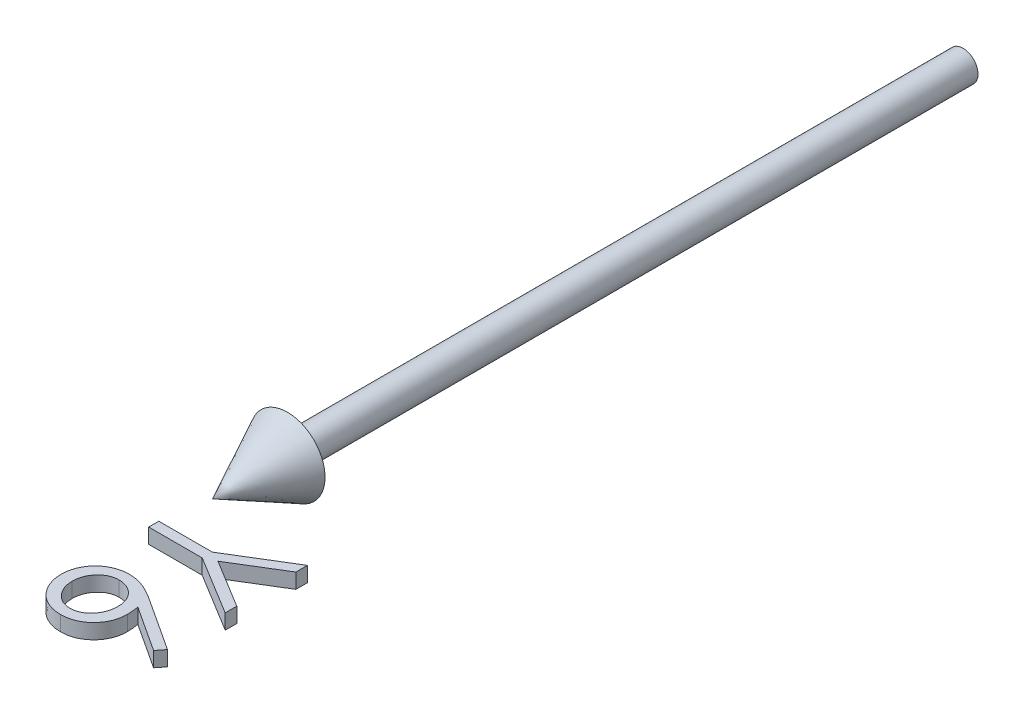
SolidWorks part; units mm, degrees
ref_plane "Front Plane" through (0, 0, 0) normal (0, 0, 1) x (1, 0, 0)
ref_plane "Top Plane" through (0, 0, 0) normal (0, 1, 0) x (1, 0, 0)
ref_plane "Right Plane" through (0, 0, 0) normal (1, 0, 0) x (0, 0, -1)
sketch "Sketch2" plane through (0, 0, 0) normal (0, 1, 0) x (1, 0, 0)
  line L0 (0, 41.95) -> (0, -114.4521) construction
  line L1 (-36.8894, 0) -> (41.4965, 0) construction
  line L2 (0, -100) -> (5, -90)
  line L3 (5, -90) -> (2, -90)
  line L4 (2, -90) -> (2, 0)
  line L5 (2, 0) -> (0, 0)
  line L6 (0, 0) -> (0, -100)
  dimension "D1" = 100
  dimension "D2" = 2
  dimension "D3" = 10
  dimension "D4" = 5
revolve "Revolve1" add sketch "Sketch2" angle 360 about L0
sketch "Sketch3" plane through (0, 0, 0) normal (0, 1, 0) x (1, 0, 0)
  line L0 (0, -101.5706) -> (0, -127.8138) construction
  text T0 "Y6\r\n\r\n\r\n" font "Century Gothic" height 15
extrude "Boss-Extrude1" add sketch "Sketch3" against normal blind 1 and the other way blind 1 separate body
equation "\"frame_arrow_length\"=100"
equation "\"D1@Sketch2\"=\"frame_arrow_length\""
equation "\"frame_arrow_odA\"=4"
equation "\"D2@Sketch2\"=\"frame_arrow_odA\"/2"
equation "\"frame_arrow_head_od\"=5"
equation "\"D4@Sketch2\"=\"frame_arrow_head_od\""
equation "\"frame_arrow_head_length\"=10"
equation "\"D3@Sketch2\"=\"frame_arrow_head_length\""
equation "\"tvarobot_theta1\"=30"
equation "\"link0_ringA_odA\"= 40"
equation "\"link0_ringA_odB\"= 25"
equation "\"link0_ringA_id\"= 20"
equation "\"link0_ringA_thickness\"= (\"link0_ringA_odB\" - \"link0_ringA_id\")/2"
equation "\"link0_ringA_height\"= 3"
equation "\"link0_ringA_heightA\"= 1.5"
equation "\"link0_ringA_heightB\"=\"link0_ringA_height\"-\"link0_ringA_heightA\""
equation "\"link0_ringB_odA\"= 40"
equation "\"link0_ringB_odB\"= 29"
equation "\"link0_ringB_id\"= \"link0_shaftA_bearing_id\"+1"
equation "\"link0_ringB_thickness\"= (\"link0_ringB_odB\" - \"link0_ringB_id\")/2"
equation "\"link0_ringB_height\"= 3"
equation "\"link0_ringB_heightA\"= 1.5"
equation "\"link0_ringB_heightB\"=\"link0_ringB_height\"-\"link0_ringB_heightA\""
equation "\"link0_shaftA_bearing_od\"=27"
equation "\"link0_shaftA_bearing_id\"=20"
equation "\"link0_shaftA_thrust_bearing_od\"=35"
equation "\"link0_shaftA_thrust_bearing_id\"=20.04"
equation "\"link0_shaftA_retaining_ring_id\"=18.5"
equation "\"link0_shaftA_retaining_ring_groove_width\"=1.5"
equation "\"link0_shaftA_spline_length\"=8.0"
equation "\"link0_shaftA_spline_depth\"=1.0"
equation "\"link0_shaftA_spline_width\"=4.0"
equation "\"link0_shaftA_odA\"=\"link0_shaftA_bearing_id\""
equation "\"link0_shaftA_odB\"=35"
equation "\"link0_shaftA_odC\"=\"link0_shaftA_bearing_id\""
equation "\"link0_shaftA_odD\"=\"link0_shaftA_odC\"-2*\"link0_shaftA_spline_depth\""
equation "\"link0_shaftA_odE\"=\"link0_shaftA_bearing_id\""
equation "\"link0_shaftA_odF\"=\"link0_shaftA_odE\"-2*\"link0_shaftA_spline_depth\""
equation "\"link0_shaftA_idA\"=10"
equation "\"link0_shaftA_idB\"=6"
equation "\"link0_shaftA_length\"=39.5"
equation "\"link0_shaftA_lengthA\"=8.0"
equation "\"link0_shaftA_lengthB\"=12.0"
equation "\"link0_shaftA_lengthC\"=35.0"
equation "\"link0_shaftA_lengthD\"=39.0"
equation "\"link0_shaftA_lengthE\"=\"link0_shaftA_length\"-\"link0_shaftA_lengthD\""
equation "\"link0_shaftA_offsetX\"=11"
equation "\"link0_shaftA_offsetY\"=0"
equation "\"link0_shaftA_bolt_pattern_dia\"=14"
equation "\"link0_motor_center_dist\"=26"
equation "\"link0_46t_pulley_spline_length\"=8"
equation "\"link0_46t_pulley_spline_depth\"=\"link0_shaftA_spline_depth\"*1.025"
equation "\"link0_46t_pulley_spline_width\"=\"link0_shaftA_spline_width\"*1.05"
equation "\"link0_46t_pulley_idA\"=\"link0_shaftA_bearing_id\"*1.025"
equation "\"link0_46t_pulley_idB\"=\"link0_46t_pulley_idA\"-2*\"link0_46t_pulley_spline_depth\""
equation "\"link0_shaftB_spline_length\"=10"
equation "\"link0_shaftB_spline_depth\"=1.0"
equation "\"link0_shaftB_spline_width\"=1.25"
equation "\"link0_shaftB_length\"=7"
equation "\"link0_shaftB_lengthA\"=1.5"
equation "\"link0_shaftB_lengthB\"=2.75"
equation "\"link0_shaftB_odA\"=32"
equation "\"link0_shaftB_odB\"=22"
equation "\"link0_shaftB_odC\"=20"
equation "\"link0_shaftB_idA\"=10"
equation "\"link0_shaftB_bolt_diameter\"=19"
equation "\"link0_shaftB_bearing_od\"=27"
equation "\"link0_shaftB_bearing_id\"=20"
equation "\"link0_motor_length\"=46.5"
equation "\"link0_motor_width\"=28.5"
equation "\"link0_motor_height\"=34"
equation "\"link0_motor_offset\"=8"
equation "\"link0_shellA_thickness\"=2.5"
equation "\"link0_shellB_thickness\"=\"link0_shellA_thickness\""
equation "\"link0_plateA_shellA_height\"=48"
equation "\"link0_shellA_width\" =\"link0_plateA_width\""
equation "\"link0_shellA_height\" = \"link0_plateA_shellA_height\"-\"link0_plateA_height\""
equation "\"link0_shellA_length\" = \"link0_plateA_lengthB\" "
equation "\"link0_shellB_length\"=\"link0_shellA_length\""
equation "\"link0_shellA_radius\" = 0.375*25.4"
equation "\"link0_shellA_radiusA\"= \"link0_plateA_radiusA\""
equation "\"link0_shellA_radiusB\"= \"link0_plateA_radiusB\""
equation "\"link0_shellA_radiusC\"= 3"
equation "\"link0_postA_height\"=7"
equation "\"link0_postA_width\"=16"
equation "\"link0_postA_length\"=20"
equation "\"link0_postA_posX\"=22"
equation "\"link0_postA_posY\"=17.5"
equation "\"link0_postA_pocket_width\"=6.0"
equation "\"link0_postA_pocket_length\"=2.5"
equation "\"link0_postA_pocket_depth\"=9"
equation "\"link0_postA_pocket_posZ\"=10"
equation "\"link0_postB_height\"=7"
equation "\"link0_postB_width\"=16"
equation "\"link0_postB_length\"=20"
equation "\"link0_postB_posX\"=22"
equation "\"link0_postB_posY\"=17.5"
equation "\"link0_postB_id\"=3.0"
equation "\"link0_postB_pocket_width\"=6.0"
equation "\"link0_postB_pocket_length\"=2.5"
equation "\"link0_postB_pocket_depth\"=9"
equation "\"link0_postB_pocket_posZ\"=10"
equation "\"link0_postC_height\"=7"
equation "\"link0_postC_width\"=16"
equation "\"link0_postC_length\"=20"
equation "\"link0_postC_posX\"=22"
equation "\"link0_postC_posY\"=17.5"
equation "\"link0_postC_id\"=3.0"
equation "\"link0_postC_pocket_width\"=6.0"
equation "\"link0_postC_pocket_length\"=2.5"
equation "\"link0_postC_pocket_depth\"=9"
equation "\"link0_postC_pocket_posZ\"=10"
equation "\"link0_postD_height\"=7"
equation "\"link0_postD_width\"=16"
equation "\"link0_postD_length\"=20"
equation "\"link0_postD_posX\"=22"
equation "\"link0_postD_posY\"=17.5"
equation "\"link0_postD_id\"=3.0"
equation "\"link0_postD_pocket_width\"=6.0"
equation "\"link0_postD_pocket_length\"=3.0"
equation "\"link0_postD_pocket_depth\"=9"
equation "\"link0_postD_pocket_posZ\"=10"
equation "\"link0_postE_height\"=5"
equation "\"link0_postE_width\"=16"
equation "\"link0_postE_length\"=\"link0_plateE_lengthA\"-\"link0_lip_height\""
equation "\"link0_postE_posZ\"=22"
equation "\"link0_postE_posX\"=17.5"
equation "\"link0_postE_posY\"=22"
equation "\"link0_postE_id\"=3.0"
equation "\"link0_postE_cbore_id\"=6.5"
equation "\"link0_postE_hole_id\"=3"
equation "\"link0_postF_posZ\"=22"
equation "\"link0_postF_posX\"=17.5"
equation "\"link0_postF_posY\"=\"link0_plateB_lengthA\"+4"
equation "\"link0_postF_id\"=3.0"
equation "\"link0_postF_cbore_id\"=6.5"
equation "\"link0_postF_hole_id\"=3"
equation "\"link0_postG_posZ\"=22"
equation "\"link0_postG_posX\"=17.5"
equation "\"link0_postG_posY\"=\"link0_plateB_lengthA\"+12"
equation "\"link0_postG_id\"=3.0"
equation "\"link0_postG_cbore_id\"=6.5"
equation "\"link0_postG_hole_id\"=3"
equation "\"link0_postHIJ_posY\"=6"
equation "\"link0_postH_posX\"=28"
equation "\"link0_postH_posY\"=20"
equation "\"link0_postH_posZ\"=20"
equation "\"link0_postH_length\"=10"
equation "\"link0_postI_posX\"=28"
equation "\"link0_postI_posY\"=20"
equation "\"link0_postI_posZ\"=135"
equation "\"link0_postI_length\"=10"
equation "\"link0_postJ_posX\"=28"
equation "\"link0_postJ_posY\"=20"
equation "\"link0_postJ_posZ\"=175"
equation "\"link0_postJ_length\"=10"
equation "\"link0_postK_posX\"=28"
equation "\"link0_postK_posY\"=20"
equation "\"link0_postK_posZ\"=175"
equation "\"link0_postK_length\"=10"
equation "\"link0_postL_posX\"=28"
equation "\"link0_postL_posY\"=20"
equation "\"link0_postL_posZ\"=135"
equation "\"link0_postL_length\"=10"
equation "\"link0_postM_posX\"=28"
equation "\"link0_postM_posY\"=20"
equation "\"link0_postM_posZ\"=35"
equation "\"link0_postM_length\"=10"
equation "\"link0_plateA_lengthA\"=30"
equation "\"link0_plateA_lengthB\"=150"
equation "\"link0_plateA_lengthC\"=30"
equation "\"link0_plateA_length\"=\"link0_plateA_lengthA\"+\"link0_plateA_lengthB\"+\"link0_plateA_lengthC\""
equation "\"link0_plateA_width\"=  68"
equation "\"link0_plateA_height\"= \"link0_plateA_radiusA\""
equation "\"link0_plateA_thickness\"=\"link0_shellA_thickness\""
equation "\"link0_plateA_radius\"= 9.5"
equation "\"link0_plateA_radiusA\"= 18"
equation "\"link0_plateA_radiusB\"= 18"
equation "\"link0_plateA_radiusC\"= 3"
equation "\"link0_plateB_length\"= 40"
equation "\"link0_plateB_width\"= \"link0_plateA_width\"*1.005"
equation "\"link0_plateB_height\"= \"link0_plateA_shellA_height\"*1.005"
equation "\"link0_plateB_lengthA\"=\"link0_lip_height\"+\"link0_plateD_thickness\"+\"link0_motor_mount_thickness\""
equation "\"link0_plateB_lengthB\"=\"link0_plateB_height\"-\"link0_plateB_lengthA\""
equation "\"link0_plateB_radiusA\"= \"link0_plateA_radiusA\""
equation "\"link0_plateB_radiusB\"= \"link0_plateA_radiusB\""
equation "\"link0_plateB_radiusC\"= 3"
equation "\"link0_plateB_idA\"=\"link0_shaftA_odC\"+1"
equation "\"link0_plateB_idB\"=\"link0_shaftA_bearing_od\"-2"
equation "\"link0_plateB_idC\"=\"link0_shaftA_bearing_od\"*1.005"
equation "\"link0_plateB_idD\"=\"link0_shaftA_thrust_bearing_od\"+1 "
equation "\"link0_plateB_depthA\"=1.0"
equation "\"link0_plateB_depthB\"=2.0"
equation "\"link0_plateB_depthC\"=8"
equation "\"link0_plateB_depthD\"=\"link0_plateB_length\"-\"link0_lip_height\"-\"link0_plateD_thickness\" "
equation "\"link0_plateC_length\"=\"link0_plateB_length\""
equation "\"link0_plateC_width\"= \"link0_plateB_width\""
equation "\"link0_plateC_height\"= .1*25.4"
equation "\"link0_plateA_hole_od\" = 0.1*25.4"
equation "\"link0_plateA_hole_delx\" = 0.5*25.4"
equation "\"link0_plateA_hole_delz\" = 0.75*25.4"
equation "\"link0_plateA_hole_offx\" = 0.0*25.4"
equation "\"link0_plateA_hole_offz\" = \"link0_plateA_length\"/2"
equation "\"link0_plateB_hole_od\" = 0.1*25.4"
equation "\"link0_plateB_hole_delx\"= 0.75*25.4"
equation "\"link0_plateB_hole_delz\"= 0.75*25.4"
equation "\"link0_plateB_hole_offx\"= 0.0*25.4"
equation "\"link0_plateB_hole_offz\"= 0.0*25.4"
equation "\"link0_plateC_hole_od\"= 0.1*25.4"
equation "\"link0_plateC_hole_delx\"= 0.75*25.4"
equation "\"link0_plateC_hole_delz\"= 0.75*25.4"
equation "\"link0_plateC_hole_offx\"= 0.0*25.4"
equation "\"link0_plateC_hole_offz\"= 0.0*25.4"
equation "\"link0_plateD_height\"=\"link0_plateB_height\"-2*\"link0_shellA_thickness\""
equation "\"link0_plateD_width\"=\"link0_plateB_width\"-2*\"link0_shellA_thickness\""
equation "\"link0_plateD_thickness\"=10"
equation "\"link0_plateD_radiusA\"=\"link0_plateB_radiusA\"-\"link0_shellA_thickness\""
equation "\"link0_plateD_odA\"= .375*25.4"
equation "\"link0_plateD_odB\"= .375*25.4"
equation "\"link0_plateD_bearing_id\"=20"
equation "\"link0_plateD_bearing_od\"=27"
equation "\"link0_plateE_radiusA\"=\"link0_plateA_radiusA\""
equation "\"link0_plateE_radiusB\"=\"link0_plateA_radiusB\""
equation "\"link0_plateE_radiusC\"=8.0"
equation "\"link0_plateE_length\"=30"
equation "\"link0_plateE_lengthA\"=16"
equation "\"link0_plateE_height\"=\"link0_plateB_height\""
equation "\"link0_plateE_width\"=\"link0_plateB_width\""
equation "\"link0_plateE_odA\"=\"gantry_coupler_id\"*0.99"
equation "\"link0_plateE_idA\"=\"link0_plateE_odA\"-20.0"
equation "\"link0_plateE_spline_depth\"=\"link0_poleA_spline_depth\"*1.05"
equation "\"link0_plateE_spline_width\"=\"link0_poleA_spline_width\"*1.075"
equation "\"link0_plateE_spline_length\"=\"link0_poleA_spline_length\""
equation "\"link0_plateE_coupler_length\"=46"
equation "\"link0_lip_height\"=5.0"
equation "\"link0_lip_thickness\"=2.0"
equation "\"link0_motor_mount_thickness\"=8.0"
equation "\"link0_motor_mount_idA\"=22"
equation "\"link0_motor_mount_idB\"=\"link0_shaftB_bearing_od\"*1.005"
equation "\"link0_motor_mount_idC\"=\"link0_shaftB_bearing_od\"-2"
equation "\"link0_motor_mount_depthA\"=5.5"
equation "\"link0_motor_mount_height\"=\"link0_plateD_height\""
equation "\"link0_motor_mount_width\"=\"link0_plateD_width\""
equation "\"link0_motor_mountL_height\"=36"
equation "\"link0_motor_mountL_heightA\"=12"
equation "\"link0_motor_mountL_length\"=50"
equation "\"link0_motor_mountL_lengthA\"=36"
equation "\"gantry_coupler_od\"=25.4*2.0"
equation "\"gantry_coupler_id\"=1.645*25.4"
equation "\"gantry_coupler_offsetX\"=\"link0_plateE_width\"/2"
equation "\"link0_poleA_odA\"=20"
equation "\"link0_poleA_odB\"=36"
equation "\"link0_poleA_idA\"=\"link0_poleA_odA\"-2*\"link0_poleA_thickness\""
equation "\"link0_poleA_idB\"=(\"link0_plateE_idA\"/2+1.5*\"link0_lip_thickness\")*1.04"
equation "\"link0_poleA_thickness\"=3.5"
equation "\"link0_poleA_length\"=100"
equation "\"link0_poleA_lengthA\"=18.5"
equation "\"link0_poleA_lengthB\"=80"
equation "\"link0_poleA_gasket_thickness\"=1.5"
equation "\"link0_poleA_spline_depth\"=1.0"
equation "\"link0_poleA_spline_width\"=4.0"
equation "\"link0_poleA_spline_length\"=10.0"
equation "\"link1_plateB_length\"=30"
equation "\"link1_lip_height\"=\"link0_lip_height\""
equation "\"link0_tension_plateA_width\"=12"
equation "\"link0_tension_plateA_lengthA\"=10.5"
equation "\"link0_tension_plateB_width\"=\"link0_tension_plateA_width\""
equation "\"link0_tension_plateB_lengthA\"=\"link0_tension_plateA_lengthA\""
equation "\"link0_tension_wheelA_posZ\"=7"
equation "\"link0_tension_wheelA_posX\"=\"link0_plateD_height\"/2-\"link0_tension_plateA_lengthA\""
equation "\"link0_m2_clear_hole_id\"=2.35"
equation "\"link0_m2_insert_hole_id\"=2.5"
equation "\"link0_m2_tap_hole_id\"=1.75"
equation "\"link0_m2_nut_socket_width\"=4.25"
equation "\"link0_m2_nut_socket_depth\"=2.5"
equation "\"link0_m2_cbore_id\"=3.75"
equation "\"link0_m2_cbore_depth\"=7"
equation "\"link0_m2_5_clear_hole_id\"=2.75"
equation "\"link0_m2_5_insert_hole_id\"=2.75"
equation "\"link0_m2_5_tap_hole_id\"=2.25"
equation "\"link0_m2_5_nut_socket_width\"=5.25"
equation "\"link0_m2_5_nut_socket_depth\"=2.5"
equation "\"link0_m2_5_cbore_id\"=4.75"
equation "\"link0_m2_5_cbore_depth\"=2.5"
equation "\"link0_m2_5_insert_access_length\"=6.0"
equation "\"link0_m2_5_insert_access_width\"=3.0"
equation "\"link0_m3_clear_hole_id\"=3.25"
equation "\"link0_m3_insert_hole_id\"=3"
equation "\"link0_m3_tap_hole_id\"=2.75"
equation "\"link0_m3_nut_socket_width\"=5.75"
equation "\"link0_m3_nut_socket_depth\"=4.0"
equation "\"link0_m3_cbore_id\"=5.75"
equation "\"link0_m3_cbore_depth\"=3.5"
equation "\"link0_m3_insert_access_length\"=4.5"
equation "\"link0_m3_insert_access_width\"=3.5"
equation "\"link0_rpi_mount_height\"=6"
equation "\"link0_rpi_mount_width\"=49"
equation "\"link0_rpi_mount_length\"=58"
equation "\"link0_rpi_mount_post_od\"=6"
equation "\"link0_rpi_mount_posZ\"=72"
equation "\"link0_rpi_mount_posX\"=11.5"
equation "\"link0_mcu_mount_height\"=5"
equation "\"link0_mcu_mount_width\"=49"
equation "\"link0_mcu_mount_length\"=58"
equation "\"link0_mcu_mount_post_od\"=6"
equation "\"link0_mcu_mount_posZ\"=164"
equation "\"link0_mcu_mount_posX\"=4"
equation "\"link0_pwr_mount_height\"=4"
equation "\"link0_pwr_mount_width\"=15.75"
equation "\"link0_pwr_mount_length\"=75.75"
equation "\"link0_pwr_mount_post_od\"=6"
equation "\"link0_pwr_mount_posZ\"=75"
equation "\"link0_pwr_mount_posX\"=16"
equation "\"link0_pwr_board_height\"=6"
equation "\"link0_pwr_board_width\"=21"
equation "\"link0_pwr_board_length\"=80"
